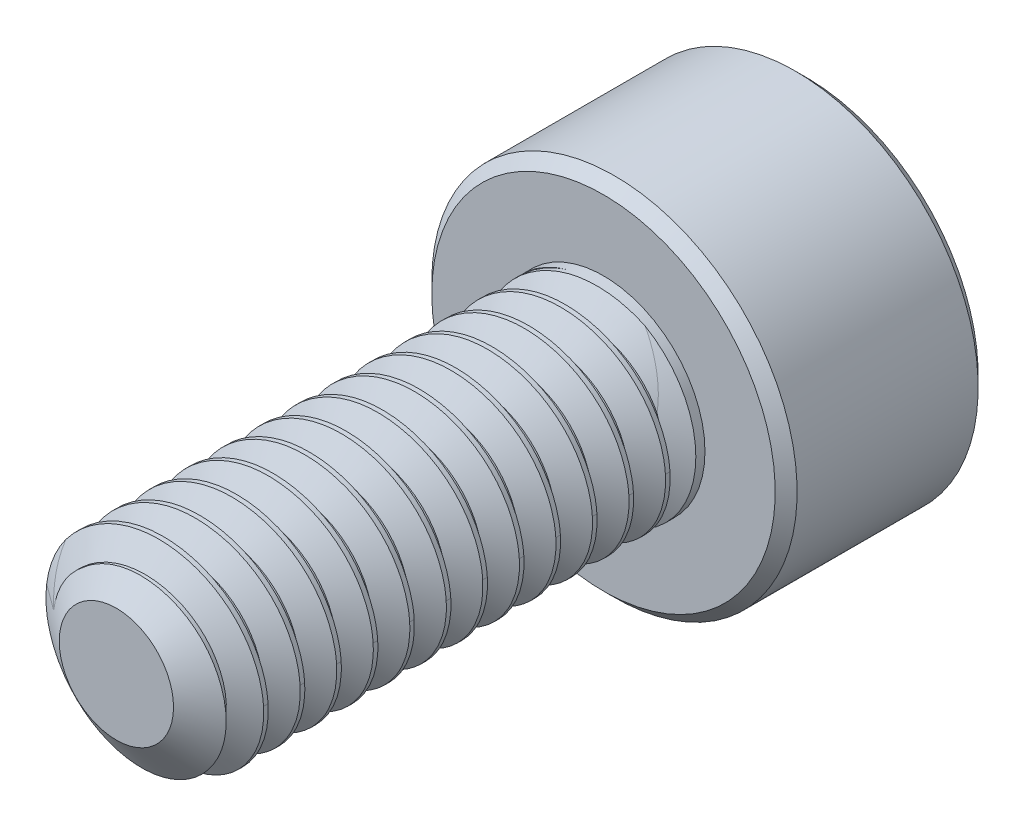
SolidWorks part; units mm, degrees
ref_plane "Front Plane" through (0, 0, 0) normal (0, 0, 1) x (1, 0, 0)
ref_plane "Top Plane" through (0, 0, 0) normal (0, 1, 0) x (1, 0, 0)
ref_plane "Right Plane" through (0, 0, 0) normal (1, 0, 0) x (0, 0, -1)
sketch "Sketch1" plane through (0, 0, 0) normal (0, 0, 1) x (1, 0, 0)
  circle A0 centre (0, 0) radius 1.25
  dimension "OD" = 2.5
extrude "Extrude1" add sketch "Sketch1" against normal blind 6
sketch "Sketch2" plane through (0, 0, 0) normal (0, 0, 1) x (1, 0, 0)
  circle A0 centre (0, 0) radius 1.25 construction
  circle A1 centre (0, 0) radius 1.25
curve "Helix/Spiral1" pitch 0.45 height 6.45 radius 1.25 centre (0, 0, 0) axis (0, 0, -1) start towards (0, 1, 0) parameters "pitch"=0.45
sketch "Sketch3" plane through (0, 0, 0) normal (1, 0, 0) x (0, 0, -1)
  line L0 (-0.3938, 1.25) -> (-0.225, 0.9577)
  line L1 (-0.225, 0.9577) -> (-0.1688, 0.9577)
  line L2 (-0.1688, 0.9577) -> (0, 1.25)
  line L3 (-0.3938, 1.25) -> (0, 1.25)
  line L4 (-0.1969, 1.25) -> (-0.1969, 0.9577) construction
  line L5 (-0.3094, 1.1039) -> (-0.0844, 1.1039) construction
  line L6 (0, 1.25) -> (0, -1.25) construction
  line L7 (0, -1.25) -> (6, -1.25) construction
  point P11 (2.025, -1.25)
  dimension "D1" = 0.0563
  dimension "D2" = 0.225
  dimension "D3" = 60
  dimension "D4" = 2.025
sweep "Cut-Sweep1" cut profiles "Sketch3" path "Helix/Spiral1" align with end faces yes
sketch "Sketch4" plane through (0, 0, 0) normal (1, 0, 0) x (0, 0, -1)
  line L0 (0.3825, 1.25) -> (0, 0.7037)
  line L1 (0, 0.7037) -> (0, 1.25)
  line L2 (0.3825, 1.25) -> (0, 1.25)
  line L3 (-0.3938, 1.25) -> (0, 1.25) construction
  line L4 (0, 0) -> (7.0209, 0) construction
  dimension "D1" = 55
  dimension "D2" = 0.254
revolve "Cut-Revolve1" cut sketch "Sketch4" angle 360 about L4
sketch "Sketch5" plane through (0, 0, 0) normal (1, 0, 0) x (0, 0, -1)
  line L0 (6, 0.3125) -> (6, 1.0937) construction
  line L1 (6, 1.25) -> (0.1203, 1.25)
  line L2 (6, 1.25) -> (6, 0)
  line L3 (6, 0) -> (0.0001, 0)
  line L4 (0.0001, 0.9198) -> (0.0001, 0)
  line L5 (0.1203, 1.25) -> (0.0001, 0.9198)
  line L6 (0, 0) -> (9.9695, 0) construction
  point P3 (0.0001, 1.25)
  point P10 (0.0001, 1.25)
  dimension "D1" = 0.3302
  dimension "Thread min" = 0.0001
  dimension "D3" = 20
revolve "partially thread" [suppressed] add sketch "Sketch5" angle 360 about L6
sketch "Sketch6" plane through (0, 0, -6) normal (0, 0, -1) x (-1, 0, 0)
  circle A0 centre (0, 0) radius 2.25
  dimension "head dia" = 4.5
extrude "Extrude2" add sketch "Sketch6" along normal blind 2.5
sketch "Sketch7" plane through (0, 0, -8.5) normal (0, 0, -1) x (-1, 0, 0)
  line L1 (0, 1.1547) -> (-1, 0.5774)
  line L2 (-1, 0.5774) -> (-1, -0.5774)
  line L3 (-1, -0.5774) -> (0, -1.1547)
  line L4 (0, -1.1547) -> (1, -0.5774)
  line L5 (1, -0.5774) -> (1, 0.5774)
  line L6 (1, 0.5774) -> (0, 1.1547)
  circle A0 centre (0, 0) radius 1 construction
  dimension "hex dia" = 2
extrude "Cut-Extrude1" cut sketch "Sketch7" against normal blind 1.5
sketch "Sketch8" plane through (0, 0, -8.5) normal (0, 0, -1) x (-1, 0, 0)
  circle A0 centre (0, 0) radius 1.1547
extrude "Cut-Extrude2" cut sketch "Sketch8" against normal through all draft 45
chamfer "Chamfer1" distance 0.135 angle 45 2 edges at (-2.25, 0, -8.5) (-2.25, 0, -6)
sketch "Sketch9" plane through (0, 0, 0) normal (1, 0, 0) x (0, 0, -1)
  line L0 (0, 1.25) -> (0, -1.25) construction
  line L1 (2.475, 1.25) -> (2.475, -1.25) construction
  dimension "D1" = 2.475
sketch "Sketch10" plane through (0, 0, 0) normal (1, 0, 0) x (0, 0, -1)
  line L0 (6, 1.25) -> (6, 0)
  line L1 (6, 1.25) -> (5.8875, 1.25)
  line L2 (5.8875, 1.25) -> (5.3697, 0)
  line L3 (6, 0) -> (5.3697, 0)
  line L4 (6, 2.115) -> (6, -2.115) construction
  dimension "D1" = 22.5
  dimension "D2" = 0.1125
revolve "Revolve1" add sketch "Sketch10" angle 360 about L3
equation "\"D3@Helix/Spiral1\" = \"screw length@Extrude1\"+\"pitch@Helix/Spiral1\""
equation "\"D1@Sketch3\" = \"pitch@Helix/Spiral1\"*.125"
equation "\"D2@Sketch3\" = \"pitch@Helix/Spiral1\"*.5"
equation "\"D1@Cut-Extrude1\" = \"hex dia@Sketch7\"*.75"
equation "\"D1@Chamfer1\" = \"head dia@Sketch6\"*.03"
equation "\"D1@Sketch9\" = \"pitch@Helix/Spiral1\"*5.5"
equation "\"D2@Sketch10\" = \"pitch@Helix/Spiral1\"*.25"
equation "\"D4@Sketch3\" = \"pitch@Helix/Spiral1\"*4.50"
